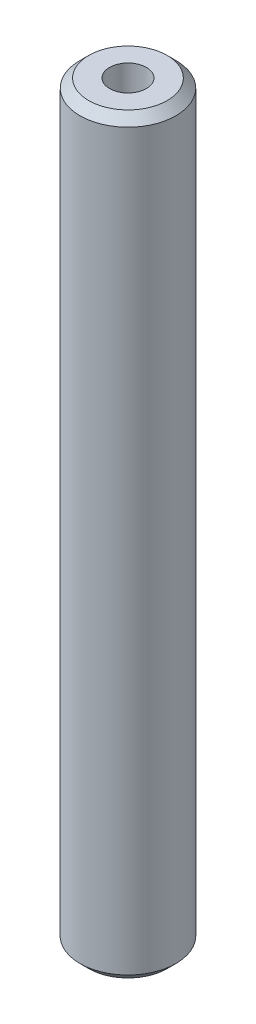
SolidWorks part; units mm, degrees
ref_plane "Front Plane" through (0, 0, 0) normal (0, 0, 1) x (1, 0, 0)
ref_plane "Top Plane" through (0, 0, 0) normal (0, 1, 0) x (1, 0, 0)
ref_plane "Right Plane" through (0, 0, 0) normal (1, 0, 0) x (0, 0, -1)
sketch "Sketch1" plane through (0, 0, 0) normal (0, 1, 0) x (1, 0, 0)
  circle A0 centre (0, 0) radius 30
  dimension "SHAFT_OD" = 60
extrude "Boss-Extrude1" add sketch "Sketch1" along normal blind 470.389
sketch "Sketch2" plane through (0, 0, 0) normal (0, 1, 0) x (1, 0, 0)
  circle A0 centre (0, 0) radius 11.5131
  dimension "BORE_D" = 23.0262
extrude "Cut-Extrude1" cut sketch "Sketch2" along normal through all
chamfer "Chamfer1" distance 5.4837 angle 45 2 edges at (0, 470.389, 30) (0, 0, 30)
